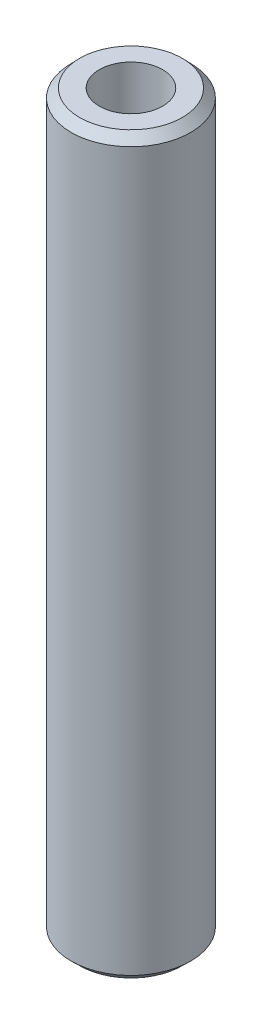
SolidWorks part; units mm, degrees
ref_plane "Front Plane" through (0, 0, 0) normal (0, 0, 1) x (1, 0, 0)
ref_plane "Top Plane" through (0, 0, 0) normal (0, 1, 0) x (1, 0, 0)
ref_plane "Right Plane" through (0, 0, 0) normal (1, 0, 0) x (0, 0, -1)
sketch "Sketch1" plane through (0, 0, 0) normal (0, 1, 0) x (1, 0, 0)
  circle A0 centre (0, 0) radius 7.5
  dimension "SHAFT_OD" = 15
extrude "Boss-Extrude1" add sketch "Sketch1" along normal blind 92.242
sketch "Sketch2" plane through (0, 0, 0) normal (0, 1, 0) x (1, 0, 0)
  circle A0 centre (0, 0) radius 3.9791
  dimension "BORE_D" = 7.9581
extrude "Cut-Extrude1" cut sketch "Sketch2" along normal through all
chamfer "Chamfer1" distance 1.0974 angle 43.919 2 edges at (0, 92.242, 7.5) (0, 0, 7.5) first distance on face at (0, 92.242, 7.5) first distance on face at (0, 0, 3.9791)
